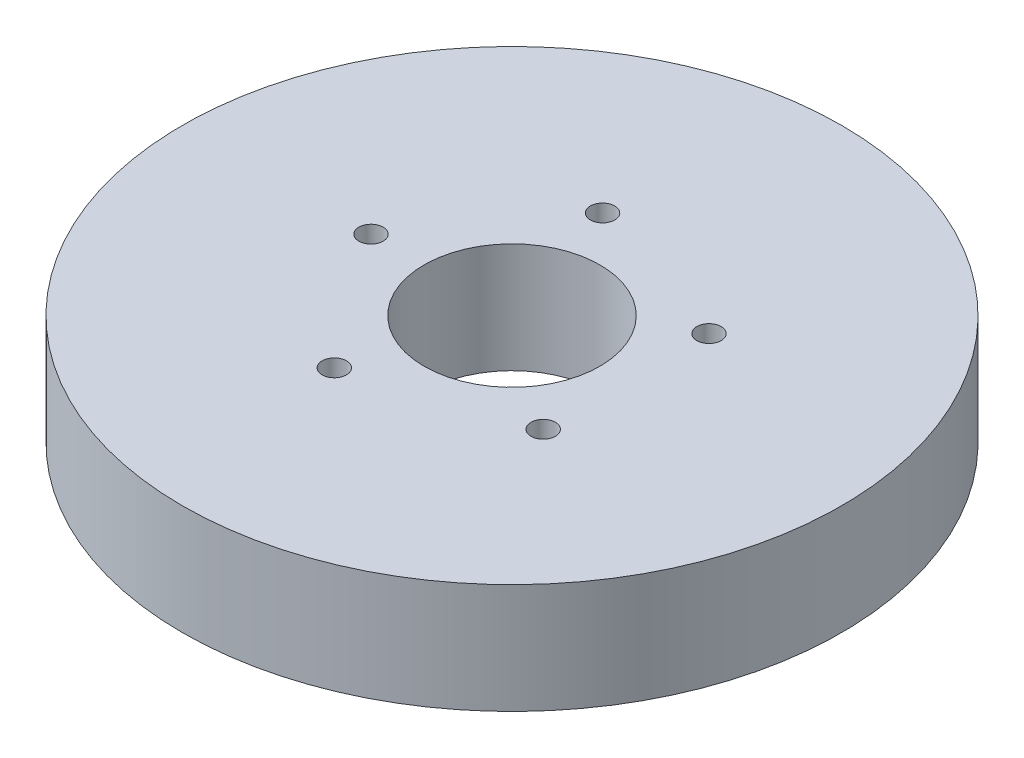
SolidWorks part; units mm, degrees
ref_plane "Front Plane" through (0, 0, 0) normal (0, 0, 1) x (1, 0, 0)
ref_plane "Top Plane" through (0, 0, 0) normal (0, 1, 0) x (1, 0, 0)
ref_plane "Right Plane" through (0, 0, 0) normal (1, 0, 0) x (0, 0, -1)
sketch "Sketch1" plane through (0, 0, 0) normal (0, 1, 0) x (1, 0, 0)
  circle A0 centre (0, 0) radius 75
  dimension "FLANGE_OD" = 150
extrude "Boss-Extrude1" add sketch "Sketch1" along normal blind 25
sketch "Sketch2" plane through (0, 0, 0) normal (0, 1, 0) x (1, 0, 0)
  circle A0 centre (0, 0) radius 20
  dimension "BORE_D" = 40
extrude "Cut-Extrude1" cut sketch "Sketch2" along normal through all
sketch "Sketch3" plane through (0, 25, 0) normal (0, 1, 0) x (1, 0, 0)
  circle A0 centre (0, 0) radius 32.0929 construction
  circle A1 centre (-32.0929, 0) radius 2.7738
  dimension "BOLT_D" = 5.5477
  dimension "BOLT_PCD" = 64.1859
extrude "Cut-Extrude2" cut sketch "Sketch3" against normal blind 20.3641
pattern_circular "CirPattern1" count 5 over 360 about axis through (0, 0, 0) along (0, 1, 0) of "Cut-Extrude2"
